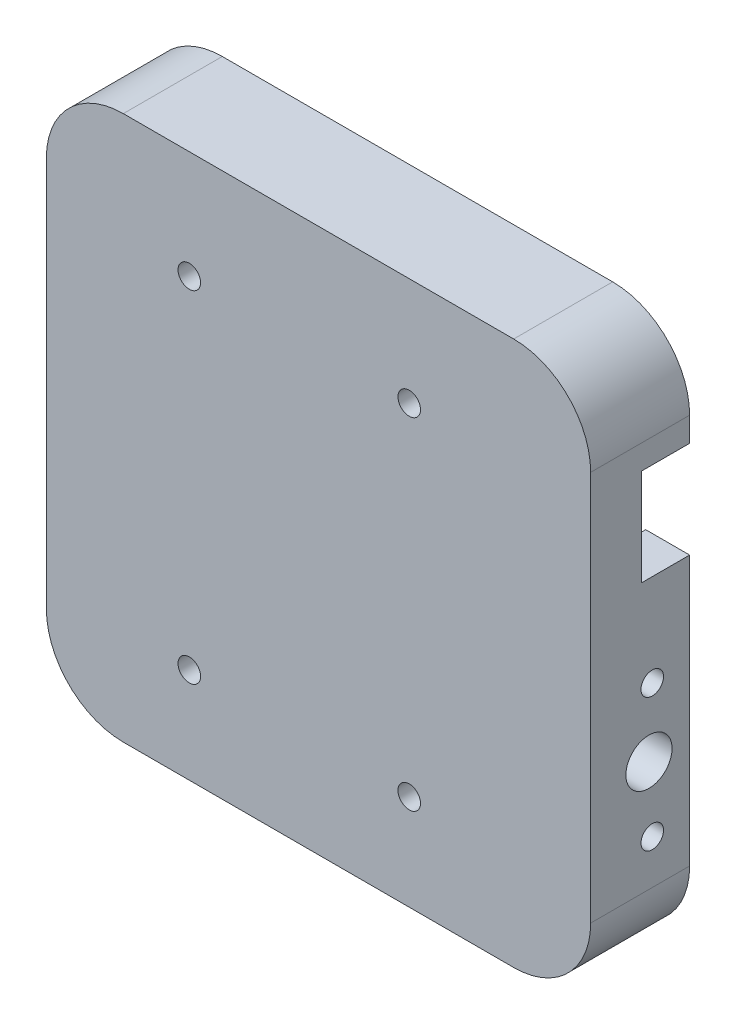
SolidWorks part; units mm, degrees
ref_plane "前视基准面" through (0, 0, 0) normal (0, 0, 1) x (1, 0, 0)
ref_plane "上视基准面" through (0, 0, 0) normal (0, 1, 0) x (1, 0, 0)
ref_plane "右视基准面" through (0, 0, 0) normal (1, 0, 0) x (0, 0, -1)
sketch "草图1" plane through (0, 0, 0) normal (0, 0, 1) x (1, 0, 0)
  line L0 (-94.518, -80.187) -> (-61.518, -80.187)
  line L1 (-95.018, -38.687) -> (-59.518, -38.687)
  line L2 (-98.018, -41.687) -> (-98.018, -77.187)
  line L3 (-95.018, -80.187) -> (-59.518, -80.187)
  line L4 (-56.518, -41.687) -> (-56.518, -77.187)
  line L5 (-98.018, -38.687) -> (-56.518, -80.187) construction
  line L6 (-98.018, -80.187) -> (-56.518, -38.687) construction
  line L7 (-98.018, -44) -> (-98.018, -62.1) construction
  line L8 (-95.018, -34.687) -> (-59.518, -34.687)
  line L9 (-52.518, -41.687) -> (-52.518, -77.187)
  line L10 (-95.018, -84.187) -> (-59.518, -84.187)
  line L11 (-102.018, -41.687) -> (-102.018, -77.187)
  arc A0 (-95.018, -38.687) -> (-98.018, -41.687) centre (-95.018, -41.687) ccw
  arc A1 (-98.018, -77.187) -> (-95.018, -80.187) centre (-95.018, -77.187) ccw
  arc A2 (-59.518, -80.187) -> (-56.518, -77.187) centre (-59.518, -77.187) ccw
  arc A3 (-59.518, -38.687) -> (-56.518, -41.687) centre (-59.518, -41.687) cw
  arc A4 (-59.518, -34.687) -> (-52.518, -41.687) centre (-59.518, -41.687) cw
  arc A5 (-59.518, -84.187) -> (-52.518, -77.187) centre (-59.518, -77.187) ccw
  arc A6 (-102.018, -77.187) -> (-95.018, -84.187) centre (-95.018, -77.187) ccw
  arc A7 (-95.018, -34.687) -> (-102.018, -41.687) centre (-95.018, -41.687) ccw
  point P0 (-77.268, -59.437)
  dimension "D3" = 3
  dimension "D1" = 41.5
  dimension "D2" = 41.5
  dimension "D4" = 4
extrude "凸台-拉伸1" add sketch "草图1" along normal blind 3 contours L8 A4 L9 A5 L10 A6 L11 A7
extrude "凸台-拉伸2" add sketch "草图1<3>" against normal blind 6 contours L8 A7 L11 A6 L10 A5 L9 A4 L1 A3 L4 A2 L3 L0 A1 L2 A0 region at (-77.268, -35.387, 0)
sketch "草图1<3>" plane through (0, 0, 0) normal (0, 0, 1) x (1, 0, 0) same geometry as "草图1"
sketch "草图2" plane through (-102.018, 0, 0) normal (-1, 0, 0) x (0, 0, 1)
  line L0 (-6, -41.687) -> (-6, -77.187) construction
  line L2 (-6.0223, -73.478) -> (0.8223, -73.478)
  line L3 (-6.0223, -73.478) -> (-6.0223, -60.778)
  line L4 (-6.0223, -60.778) -> (0.8223, -60.778)
  line L5 (0.8223, -73.478) -> (0.8223, -60.778)
  line L6 (-6.0223, -73.478) -> (0.8223, -60.778) construction
  line L7 (-6.0223, -60.778) -> (0.8223, -73.478) construction
  circle A1 centre (-2.6, -67.128) radius 2.1
  point P0 (-2.6, -67.128)
  point P9 (-2.6, -73.478)
  point P10 (-2.6, -60.778)
  dimension "D1" = 4.2
  dimension "D2" = 3.4
  dimension "D3" = 12.7
extrude "切除-拉伸1" cut sketch "草图2" against normal up to surface (4 mm away) contours A1 up to face at (-98.018, -59.437, -3)
sketch "草图3" plane through (-52.518, 0, 0) normal (1, 0, 0) x (0, 0, -1)
  line L0 (6, -41.687) -> (6, -77.187) construction
  circle A0 centre (2.3, -67.128) radius 2.1
  dimension "D1" = 4.2
  dimension "D2" = 3.7
extrude "切除-拉伸2" cut sketch "草图3" against normal up to surface (4 mm away) up to face at (-56.518, -59.437, -3)
hole_wizard "M2.5x0.45 螺纹孔1" positions "草图4" profile "草图5" tap size "M2.5x0.45" standard "ANSI Metric" end condition through all
sketch "草图4" plane through (-102.018, 0, 0) normal (-1, 0, 0) x (0, 0, 1)
  line L0 (-2.6, -66.8137) -> (-2.6, -78.9137) construction
  circle A0 centre (-2.6, -67.128) radius 6.05
  circle A1 centre (-2.6, -67.128) radius 2.1 construction
  point P0 (-2.6, -61.078)
  point P2 (-2.6, -73.178)
  dimension "D1" = 12.1
sketch "草图5" plane through (-102.018, -61.078, -2.6) normal (0, 1, 0) x (0, 0, 1)
  line L0 (0, 0) -> (0, 49.5)
  line L1 (0, 49.5) -> (1.025, 49.5)
  line L2 (1.025, 49.5) -> (1.025, 0)
  line L5 (1.025, 0) -> (0, 0)
  line L11 (0, -6.35) -> (0, 107.95) construction
  dimension "通孔螺纹孔钻头直径" = 2.05
  dimension "通孔螺纹孔钻头深度" = 49.5
cosmetic thread "孔螺蚊线1" parameters "D2"=2.5
cosmetic thread "孔螺蚊线2" parameters "D2"=2.5
sketch "草图8" plane through (0, 0, -6) normal (0, 0, -1) x (-1, 0, 0)
  line L0 (62.134, -43.902) -> (62.134, -52.702)
  line L1 (62.134, -43.902) -> (52.518, -43.902)
  line L2 (62.134, -52.702) -> (52.518, -52.702)
  line L3 (52.518, -43.902) -> (52.518, -52.702)
  line L4 (52.518, -41.687) -> (52.518, -77.187) construction
  line L6 (56.518, -41.687) -> (56.518, -77.187) construction
  line L7 (52.518, -48.302) -> (62.134, -48.302) construction
  line L8 (95.018, -34.687) -> (59.518, -34.687) construction
  dimension "D1" = 8.8
  dimension "D2" = 13.615
  dimension "D3" = 5.616
extrude "切除-拉伸3" cut sketch "草图8" against normal blind 4.4 contours L1 L3 L2 L0
hole_wizard "M2.5x0.45 螺纹孔2" positions "草图9" profile "草图10" tap size "M2.5x0.45" standard "ANSI Metric" end condition through all
sketch "草图9" plane through (0, 0, 3) normal (0, 0, 1) x (1, 0, 0)
  point P16 (-89.018, -44.497)
  point P18 (-69.018, -44.497)
  point P20 (-69.018, -75.497)
  point P22 (-89.018, -75.497)
sketch "草图10" plane through (-89.018, -44.497, 3) normal (1, 0, 0) x (0, -1, 0)
  line L0 (0, 0) -> (0, 9)
  line L1 (0, 9) -> (1.025, 9)
  line L2 (1.025, 9) -> (1.025, 0)
  line L5 (1.025, 0) -> (0, 0)
  line L11 (0, -6.35) -> (0, 107.95) construction
  dimension "通孔螺纹孔钻头直径" = 2.05
  dimension "通孔螺纹孔钻头深度" = 9
cosmetic thread "孔螺蚊线3" parameters "D2"=2.5
cosmetic thread "孔螺蚊线4" parameters "D2"=2.5
cosmetic thread "孔螺蚊线5" parameters "D2"=2.5
cosmetic thread "孔螺蚊线6" parameters "D2"=2.5
sketch "草图11" plane through (-52.518, 0, 0) normal (1, 0, 0) x (0, 0, -1)
  line L0 (1.6, -43.902) -> (1.6, -52.702) construction
  line L1 (6.2096, -55.917) -> (-3.0096, -55.917)
  line L2 (6.2096, -55.917) -> (6.2096, -40.687)
  line L3 (6.2096, -40.687) -> (-3.0096, -40.687)
  line L4 (-3.0096, -55.917) -> (-3.0096, -40.687)
  line L5 (6.2096, -55.917) -> (-3.0096, -40.687) construction
  line L6 (6.2096, -40.687) -> (-3.0096, -55.917) construction
  line L7 (-3, -34.687) -> (6, -34.687) construction
  line L9 (-3.0096, -40.687) -> (6.2096, -40.687)
  line L10 (-3.0096, -40.687) -> (-3.0096, -35.1109)
  line L11 (-3.0096, -35.1109) -> (6.2096, -35.1109)
  line L12 (6.2096, -40.687) -> (6.2096, -35.1109)
  point P0 (1.6, -48.302)
  line M8 (6, -77.187) -> (6, -52.702)
  line M9 (6, -52.702) -> (1.6, -52.702)
  line M10 (1.6, -52.702) -> (1.6, -43.902)
  line M11 (1.6, -43.902) -> (6, -43.902)
  line M12 (6, -43.902) -> (6, -41.687)
  line M13 (6, -41.687) -> (-3, -41.687)
  line M14 (-3, -41.687) -> (-3, -77.187)
  dimension "D1" = 6
extrude "切除-拉伸4" [suppressed] cut sketch "草图11" against normal blind 2 contours L3 L12 L11 L10 | L1 M8 M9 M10 M11 M12 M13 M14 | L4 L1 L2 L3 M14 M13 M12 M11 M10 M9 M8
fillet "圆角5" [suppressed] radius 1
